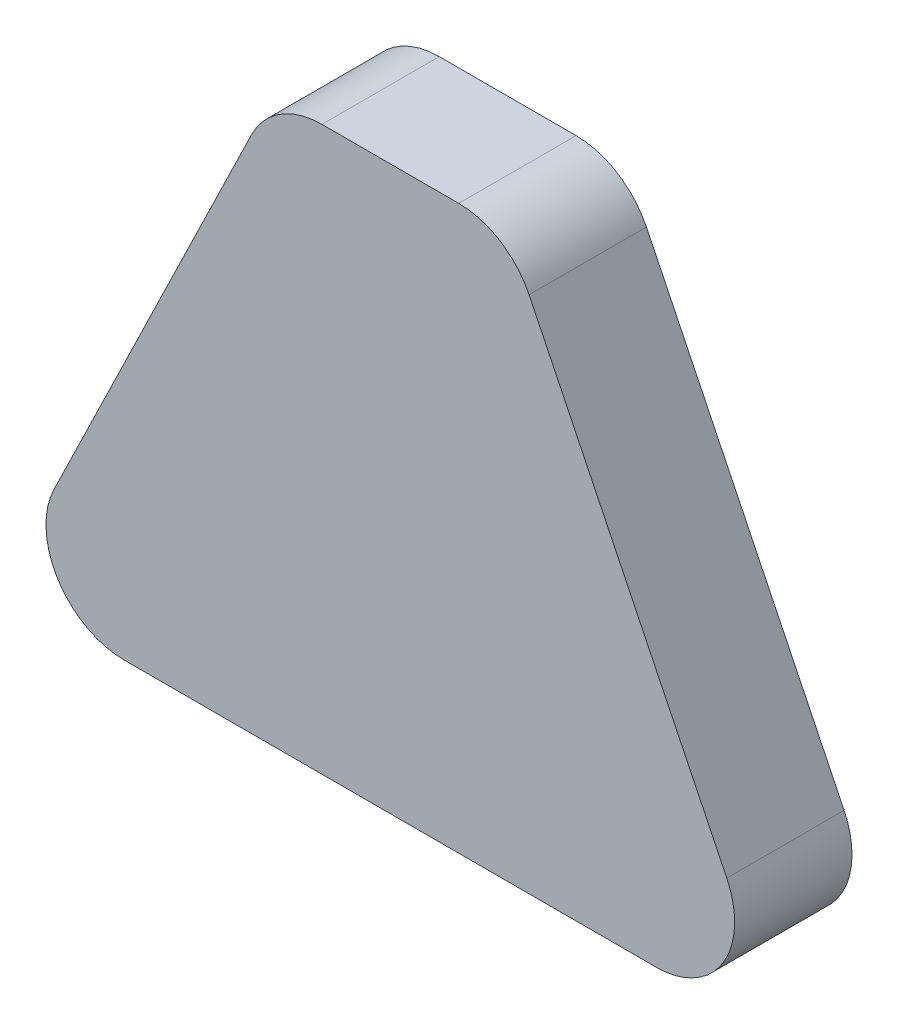
SolidWorks part; units mm, degrees
ref_plane "Front Plane" through (0, 0, 0) normal (0, 0, 1) x (1, 0, 0)
ref_plane "Top Plane" through (0, 0, 0) normal (0, 1, 0) x (1, 0, 0)
ref_plane "Right Plane" through (0, 0, 0) normal (1, 0, 0) x (0, 0, -1)
sketch "Sketch1" plane through (0, 0, 0) normal (0, 0, 1) x (1, 0, 0)
  line L0 (0, 0) -> (35, 71.9375)
  line L1 (35, 71.9375) -> (65, 71.9375)
  line L3 (100, 0) -> (0, 0)
  line L4 (50, 73.0285) -> (50, 24.2987) construction
  line L5 (100, 0) -> (65, 71.9375)
  point P8 (50, 0)
  point P9 (50, 71.9375)
  dimension "D1" = 15
  dimension "D2" = 80
  dimension "D3" = 50
extrude "Boss-Extrude1" add sketch "Sketch1" along normal blind 15 contours L5 L1 L0 L3
fillet "Fillet1" radius 10 4 edges at (0, 0, 7.5) (100, 0, 7.5) (65, 71.9375, 7.5) (35, 71.9375, 7.5)
